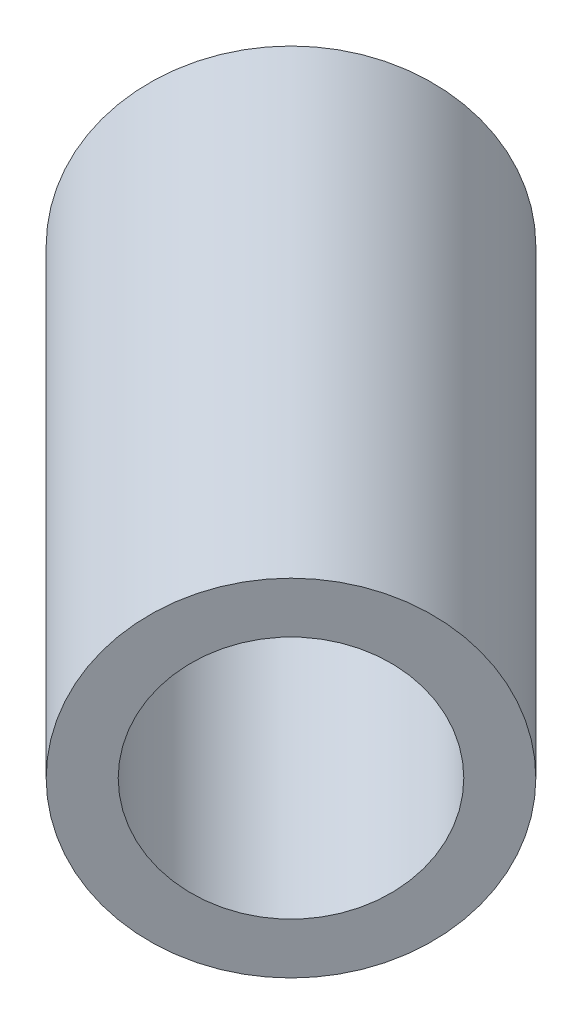
SolidWorks part; units mm, degrees
material "Silicon Rubber"
ref_plane "X-Y Datum" through (0, 0, 0) normal (0, 0, 1) x (1, 0, 0)
ref_plane "X-Z Datum" through (0, 0, 0) normal (0, 1, 0) x (1, 0, 0)
ref_plane "Y-Z Datum" through (0, 0, 0) normal (1, 0, 0) x (0, 0, -1)
sketch "Sketch1" plane through (0, 0, 0) normal (0, 1, 0) x (1, 0, 0)
  line L0 (0, 0) -> (-35.921, 35.921)
  dimension "D1" = 50.8
sweep "Sweep1" add path "Sketch1" circular profile diameter 26.9875 parameters "D3"=26.9875
sweep "Cut-Sweep1" cut path "Sketch1<3>" circular profile diameter 19.05 parameters "D3"=19.05
sketch "Sketch1<3>" plane through (0, 0, 0) normal (0, 1, 0) x (1, 0, 0) same geometry as "Sketch1"
